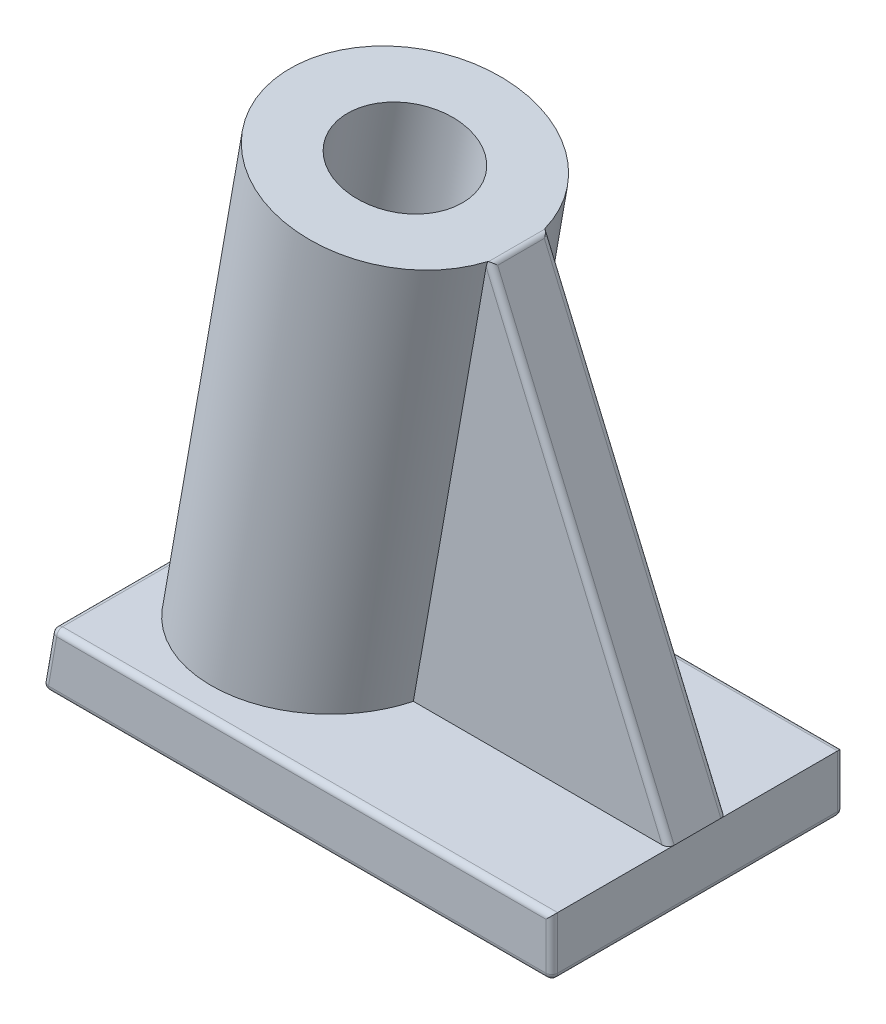
SolidWorks part; units mm, degrees
ref_plane "前视基准面" through (0, 0, 0) normal (0, 0, 1) x (1, 0, 0)
ref_plane "上视基准面" through (0, 0, 0) normal (0, 1, 0) x (1, 0, 0)
ref_plane "右视基准面" through (0, 0, 0) normal (1, 0, 0) x (0, 0, -1)
sketch "草图1" plane through (0, 0, 0) normal (0, 0, 1) x (1, 0, 0)
  line L0 (0, 0) -> (5.5, 0)
  line L1 (5.5, 0) -> (5.5, 2)
  line L2 (-12, 0) -> (-11.6473, 2)
  line L3 (-11.6473, 2) -> (5.5, 2)
  line L4 (-12, 0) -> (0, 0)
  dimension "D1" = 5.5
  dimension "D2" = 12
  dimension "D3" = 2
  dimension "D4" = 80
extrude "凸台-拉伸1" add sketch "草图1" along normal blind 5 and the other way blind 5
sketch "草图2" plane through (0, 0, 0) normal (0, 0, 1) x (1, 0, 0)
  line L0 (0, 0) -> (0, -2) construction
  line L1 (0, -2) -> (0, -2.5) construction
  line L2 (-1.5, 0) -> (1.5, 0)
  line L3 (-12, 0) -> (5.5, 0) construction
  line L4 (1.5, 0) -> (1.5, -0.6771)
  line L5 (-1.95, -2.5) -> (1.95, -2.5)
  line L6 (1.95, -2.5) -> (1.95, -1.5556)
  line L7 (-1.95, -2.5) -> (-1.95, -1.5556)
  line L8 (-1.5, 0) -> (-1.5, -0.6771)
  arc A0 (1.95, -1.5556) -> (1.5, -0.6771) centre (0, -2) ccw
  arc A1 (-1.95, -1.5556) -> (-1.5, -0.6771) centre (0, -2) cw
  dimension "D1" = 2
  dimension "D2" = 0.5
  dimension "D3" = 1.5
  dimension "D4" = 1.95
extrude "凸台-拉伸2" add sketch "草图2" along normal blind 2 and the other way blind 2
sketch "草图3" plane through (0, 0, 0) normal (1, 0, 0) x (0, 0, -1)
  line L0 (0, 0) -> (0, -2) construction
  line L1 (0, -2) -> (0, -2.5) construction
  line L2 (0, 0) -> (1.5, 0) construction
  line L3 (5, 0) -> (-5, 0) construction
  line L4 (1.5, 0) -> (1.5, -0.6771)
  line L5 (0, -2.5) -> (1.95, -2.5) construction
  line L6 (1.95, -2.5) -> (1.95, -1.5556)
  line L7 (1.95, -2.5) -> (2, -2.5)
  line L8 (2, -2.5) -> (2, 0)
  line L9 (2, 0) -> (1.5, 0)
  line L10 (-2, 0) -> (-1.5, 0)
  line L11 (-2, -2.5) -> (-2, 0)
  line L12 (-1.95, -2.5) -> (-2, -2.5)
  line L13 (-1.95, -2.5) -> (-1.95, -1.5556)
  line L14 (-1.5, 0) -> (-1.5, -0.6771)
  arc A0 (1.95, -1.5556) -> (1.5, -0.6771) centre (0, -2) ccw
  arc A1 (-1.95, -1.5556) -> (-1.5, -0.6771) centre (0, -2) cw
  dimension "D1" = 2
  dimension "D2" = 0.5
  dimension "D3" = 1.5
  dimension "D4" = 1.95
extrude "切除-拉伸1" cut sketch "草图3" against normal blind 2 and the other way blind 2
ref_plane "基准面1" through (-11.6473, 2, 5) normal (-0.1736, -0.9848, 0) x (-0.9848, 0.1736, 0)
sketch "草图5" plane through (-11.6473, 2, 5) normal (-0.1736, -0.9848, 0) x (-0.9848, 0.1736, 0)
  line L0 (0, 5) -> (-4.4, 5) construction
  line L1 (0, 10) -> (0, 0) construction
  circle A0 centre (-4.4, 5) radius 4
  circle A1 centre (-4.4, 5) radius 2
  dimension "D2" = 8
  dimension "D3" = 4
  dimension "D1" = 4.4
extrude "凸台-拉伸3" add sketch "草图5" against normal blind 16
sketch "草图6" plane through (0, 0, 0) normal (0, 0, 1) x (1, 0, 0)
  line L0 (5.5, 2) -> (-0.5966, 16.2983)
  line L1 (-0.5966, 16.2983) -> (-2.0738, 16.5588)
  line L2 (-0.5966, 16.2983) -> (-8.4751, 17.6875) construction
  line L3 (-2.0738, 16.5588) -> (-4.6409, 2)
  line L4 (5.5, 2) -> (-11.6473, 2) construction
  line L5 (-4.6409, 2) -> (5.5, 2)
  dimension "D1" = 1.5
extrude "凸台-拉伸4" add sketch "草图6" along normal blind 1 and the other way blind 1
sketch "草图7" plane through (2.7692, 15.7048, 0) normal (0.1736, 0.9848, 0) x (0.9848, -0.1736, 0)
  circle A0 centre (-7.4177, 0) radius 2.5
  dimension "D1" = 5
extrude "切除-拉伸2" cut sketch "草图7" against normal up to next from offset 16 offset against normal yes
sketch "草图8" plane through (2.7692, 15.7048, 0) normal (0.1736, 0.9848, 0) x (0.9848, -0.1736, 0)
  circle A0 centre (-7.4177, 0) radius 2
extrude "切除-拉伸3" cut sketch "草图8" against normal up to next
fillet "圆角3" radius 0.2 10 edges at (5.5, 1, -5) (-3.0737, 2, -5) (-3.25, 0, -5) (-3.0737, 2, 5) (5.5, 1, 5) (-3.25, 0, 5) (-11.8237, 1, -5) (-11.6473, 2, 0) (-11.8237, 1, 5) (-12, 0, 0)
fillet "圆角5" radius 0.2 3 edges at (5.4414, 0.0586, -4.9414) (5.4414, 0.0586, 4.9414) (5.5, 0, 0)
fillet "圆角7" radius 0.2 3 edges at (-0.5966, 16.2983, 0) (2.4517, 9.1491, -1) (2.4517, 9.1491, 1)
fillet "圆角8" radius 0.1 4 edges at (0, -2.5, 1.95) (1.95, -2.5, 0) (0, -2.5, -1.95) (-1.95, -2.5, 0)
